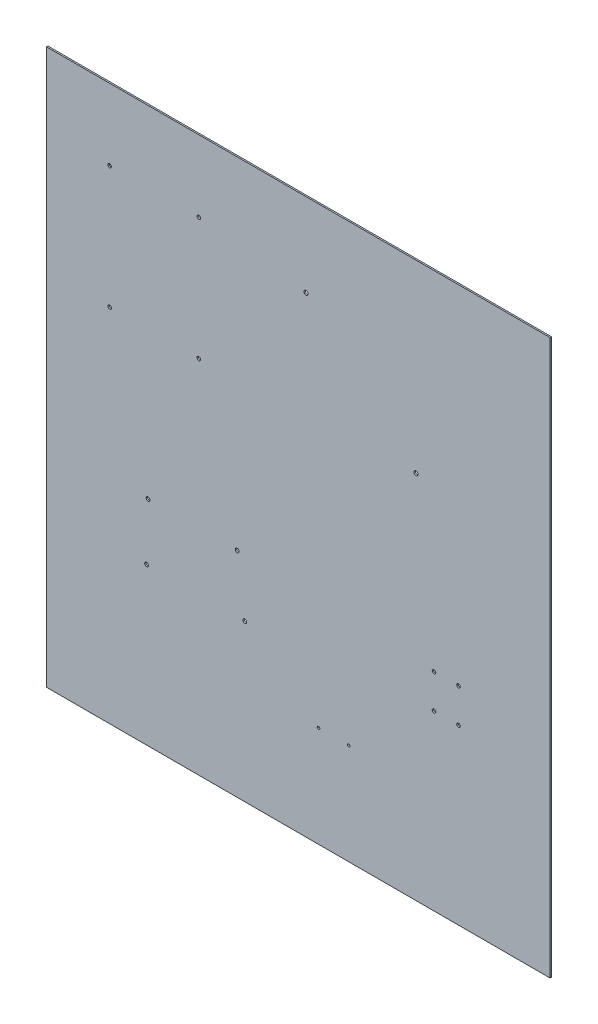
SolidWorks part; units mm, degrees
ref_plane "Plan de face" through (0, 0, 0) normal (0, 0, 1) x (1, 0, 0)
ref_plane "Plan de dessus" through (0, 0, 0) normal (0, 1, 0) x (1, 0, 0)
ref_plane "Plan de droite" through (0, 0, 0) normal (1, 0, 0) x (0, 0, -1)
sketch "Esquisse1" plane through (0, 0, 0) normal (0, 0, 1) x (1, 0, 0)
  line L1 (-62.5394, 35.2073) -> (360.4606, 35.2073)
  line L2 (-62.5394, 35.2073) -> (-62.5394, -430.7927)
  line L3 (-62.5394, -430.7927) -> (360.4606, -430.7927)
  line L4 (360.4606, 35.2073) -> (360.4606, -430.7927)
  dimension "D1" = 423
  dimension "D2" = 466
extrude "Boss.-Extru.1" add sketch "Esquisse1" along normal blind 1.2
sketch "Esquisse2" plane through (0, 0, 1.2) normal (0, 0, 1) x (1, 0, 0)
  line L0 (-62.5394, 35.2073) -> (-62.5394, -430.7927) construction
  line L1 (360.4606, 35.2073) -> (-62.5394, 35.2073) construction
  circle A0 centre (-9.5394, -24.7927) radius 1.5
  circle A1 centre (65.3906, -24.7927) radius 1.5
  circle A2 centre (65.3906, -127.6627) radius 1.5
  circle A3 centre (-9.5394, -127.6627) radius 1.5
  circle A4 centre (155.3906, -34.7927) radius 1.75
  circle A5 centre (247.8906, -119.7927) radius 1.75
  circle A6 centre (21.5278, -299.3547) radius 1.6
  circle A7 centre (103.9978, -299.3547) radius 1.6
  circle A8 centre (22.7578, -251.1347) radius 1.6
  circle A9 centre (97.6378, -251.1347) radius 1.6
  circle A10 centre (262.9748, -256.6973) radius 1.5
  circle A11 centre (262.9748, -285.2973) radius 1.5
  circle A12 centre (283.5748, -285.2973) radius 1.5
  circle A13 centre (283.5748, -256.6973) radius 1.5
  circle A14 centre (165.9543, -346.0821) radius 1.1
  circle A15 centre (191.3543, -346.0821) radius 1.1
  dimension "D1" = 3
  dimension "D2" = 53
  dimension "D5" = 85
  dimension "D6" = 92.5
  dimension "D7" = 3.5
  dimension "D8" = 3.5
  dimension "D9" = 90
  dimension "D10" = 70
  dimension "D11" = 60
  dimension "D12" = 3.2
  dimension "D13" = 3.2
  dimension "D14" = 82.47
  dimension "D15" = 48.22
  dimension "D16" = 1.23
  dimension "D17" = 3.2
  dimension "D18" = 3.2
  dimension "D19" = 74.88
  dimension "D20" = 28.6
  dimension "D21" = 20.6
  dimension "D22" = 3
  dimension "D23" = 3
  dimension "D24" = 3
  dimension "D25" = 3
  dimension "D27" = 28.6
  dimension "D28" = 25.4
  dimension "D29" = 2.2
  dimension "D30" = 2.2
  dimension "D26" = 20.6
  dimension "D3" = 2
  dimension "D4" = 2
extrude "Enlèv. mat.-Extru.1" cut sketch "Esquisse2" against normal blind 1.2
